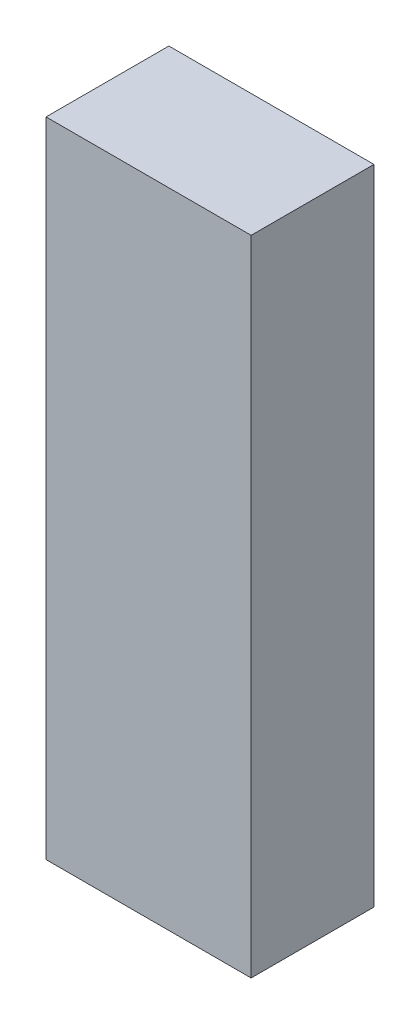
SolidWorks part; units mm, degrees
ref_plane "Front Plane" through (0, 0, 0) normal (0, 0, 1) x (1, 0, 0)
ref_plane "Top Plane" through (0, 0, 0) normal (0, 1, 0) x (1, 0, 0)
ref_plane "Right Plane" through (0, 0, 0) normal (1, 0, 0) x (0, 0, -1)
sketch "Sketch1" plane through (0, 0, 0) normal (0, 1, 0) x (1, 0, 0)
  line L1 (0, 0) -> (40.4939, 0)
  line L2 (0, 0) -> (0, 24.2514)
  line L3 (0, 24.2514) -> (40.4939, 24.2514)
  line L4 (40.4939, 0) -> (40.4939, 24.2514)
extrude "Boss-Extrude1" add sketch "Sketch1" along normal blind 127
sketch "Sketch2" plane through (0, 0, -24.2514) normal (0, 0, -1) x (-1, 0, 0)
  line L1 (-33.7019, 118.9586) -> (-5.7619, 118.9586)
  line L2 (-33.7019, 118.9586) -> (-33.7019, 6.5549)
  line L3 (-33.7019, 6.5549) -> (-5.7619, 6.5549)
  line L4 (-5.7619, 118.9586) -> (-5.7619, 6.5549)
extrude "Cut-Extrude1" cut sketch "Sketch2" against normal blind 16.764
